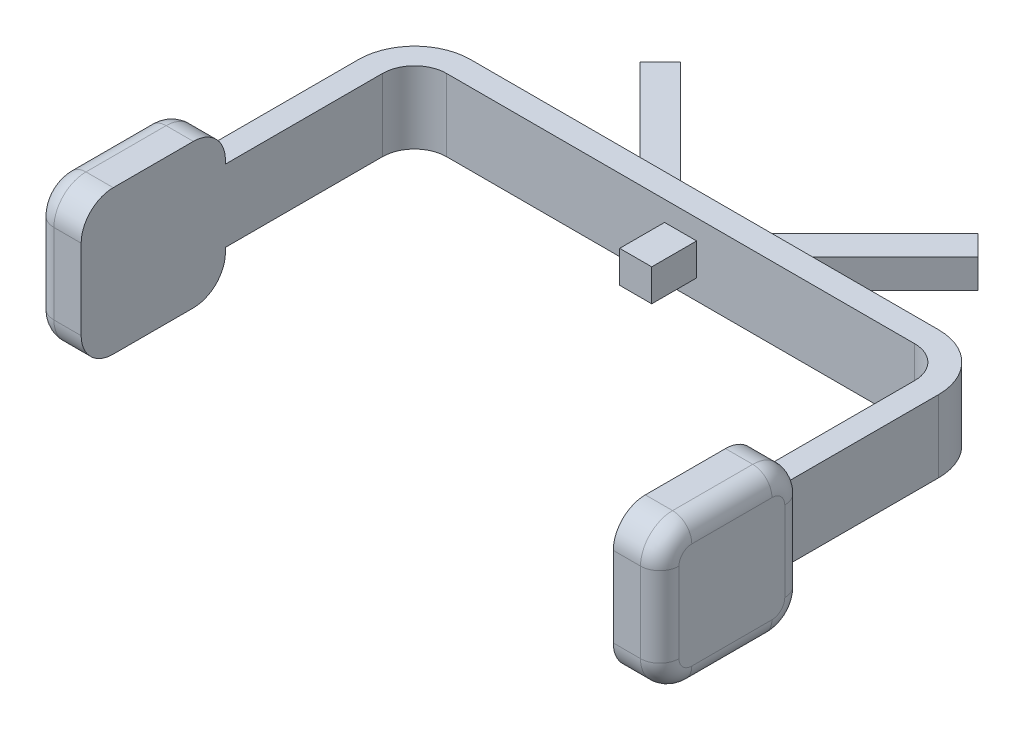
SolidWorks part; units mm, degrees
ref_plane "前视基准面" through (0, 0, 0) normal (0, 0, 1) x (1, 0, 0)
ref_plane "上视基准面" through (0, 0, 0) normal (0, 1, 0) x (1, 0, 0)
ref_plane "右视基准面" through (0, 0, 0) normal (1, 0, 0) x (0, 0, -1)
sketch "草图1" plane through (0, 0, 0) normal (0, 1, 0) x (1, 0, 0)
  line L0 (-1.5, 0) -> (1.5, 0)
  line L1 (1.5, 0) -> (9.2782, 7.7782)
  line L2 (-1.5, 0) -> (-9.2782, 7.7782)
  line L3 (-9.2782, 7.7782) -> (-10.551, 6.5054)
  line L4 (9.2782, 7.7782) -> (10.551, 6.5054)
  line L5 (-14.6, -1.5) -> (14.6, -1.5)
  line L6 (-1.5, -1.5) -> (1.5, -1.5) construction
  line L7 (-16.6, -3.5) -> (-16.6, -13.3)
  line L8 (16.6, -3.5) -> (16.6, -13.3)
  line L9 (-10.551, 6.5054) -> (-4.0456, 0)
  line L10 (10.551, 6.5054) -> (4.0456, 0)
  line L11 (-18.1, -3.5) -> (-18.1, -13.3)
  line L12 (-14.6, 0) -> (14.6, 0)
  line L13 (18.1, -3.5) -> (18.1, -13.3)
  line L14 (-18.1, -13.3) -> (-16.6, -13.3)
  line L15 (16.6, -13.3) -> (18.1, -13.3)
  line L16 (-1, -4.3) -> (-1, -1.5)
  line L17 (1, -4.3) -> (-1, -4.3)
  line L18 (1, -4.3) -> (1, -1.5)
  arc A0 (-14.6, -1.5) -> (-16.6, -3.5) centre (-14.6, -3.5) ccw
  arc A1 (16.6, -3.5) -> (14.6, -1.5) centre (14.6, -3.5) ccw
  arc A2 (-14.6, 0) -> (-18.1, -3.5) centre (-14.6, -3.5) ccw
  arc A3 (18.1, -3.5) -> (14.6, 0) centre (14.6, -3.5) ccw
  point P4 (0, 0)
  point P11 (0, 1.5)
  point P14 (0, -1.5)
  point P16 (0, -1.5)
  point P20 (0, -4.3)
  point P22 (-16.6, -1.5)
  point P25 (16.6, -1.5)
  point P39 (1.5, 0)
  point P41 (0, -4.3)
  dimension "D2" = 2
  dimension "D3" = 2
  dimension "D1" = 33.2
  dimension "D5" = 9.8
  dimension "D6" = 0
  dimension "D7" = 11
  dimension "D8" = 11
  dimension "D9" = 9.8
  dimension "D4" = 1.5
extrude "凸台-拉伸2" add sketch "草图1" along normal mid plane 4.5 contours L12 A3 L13 L15 L8 A1 L5 A0 L7 L14 L11 A2
extrude "凸台-拉伸3" add sketch "草图1<5>" along normal mid plane 2 contours L17 L18 L5 L16 region at (0, 0, 2.9)
sketch "草图1<5>" plane through (0, 0, 0) normal (0, 1, 0) x (1, 0, 0) same geometry as "草图1"
extrude "凸台-拉伸4" add sketch "草图1<6>" along normal mid plane 1.8 contours L1 L12 L10 L4 | L9 L12 L2 L3 region at (-6.3153, 0, -3.5803) region at (6.3153, 0, -3.5803)
sketch "草图1<6>" plane through (0, 0, 0) normal (0, 1, 0) x (1, 0, 0) same geometry as "草图1"
ref_plane "基准面1" through (16.6, 0, 0) normal (-1, 0, 0) x (0, 0, 1)
sketch "草图2" plane through (16.6, 0, 0) normal (-1, 0, 0) x (0, 0, 1)
  line L0 (13.3, 2.25) -> (13.3, -2.25) construction
  line L1 (13.3, 0) -> (17.8, -0.0211) construction
  line L2 (13.3, 2.25) -> (13.3, -2.25) construction
  line L3 (20.3, 4.4789) -> (15.3, 4.4789)
  line L4 (22.3, 2.4789) -> (22.3, -2.5211)
  line L5 (20.3, -4.5211) -> (15.3, -4.5211)
  line L6 (13.3, 2.4789) -> (13.3, -2.5211)
  line L7 (22.3, 4.4789) -> (13.3, -4.5211) construction
  line L8 (22.3, -4.5211) -> (13.3, 4.4789) construction
  arc A0 (15.3, 4.4789) -> (13.3, 2.4789) centre (15.3, 2.4789) ccw
  arc A1 (22.3, -2.5211) -> (20.3, -4.5211) centre (20.3, -2.5211) cw
  arc A2 (15.3, -4.5211) -> (13.3, -2.5211) centre (15.3, -2.5211) cw
  arc A3 (22.3, 2.4789) -> (20.3, 4.4789) centre (20.3, 2.4789) ccw
  dimension "D3" = 2
  dimension "D4" = 2
  dimension "D1" = 9
  dimension "D2" = 9
  dimension "D5" = 0
extrude "凸台-拉伸5" add sketch "草图2" against normal blind 2.9
fillet "圆角1" radius 1.2 8 edges at (19.5, -0.0211, 13.3) (19.5, -3.9353, 13.8858) (19.5, -4.5211, 17.8) (19.5, -3.9353, 21.7142) (19.5, -0.0211, 22.3) (19.5, 3.8931, 21.7142) (19.5, 4.4789, 17.8) (19.5, 3.8931, 13.8858)
mirror "镜向2" about plane through (0, 0, 0) normal (1, 0, 0) of "凸台-拉伸5", "圆角1"
